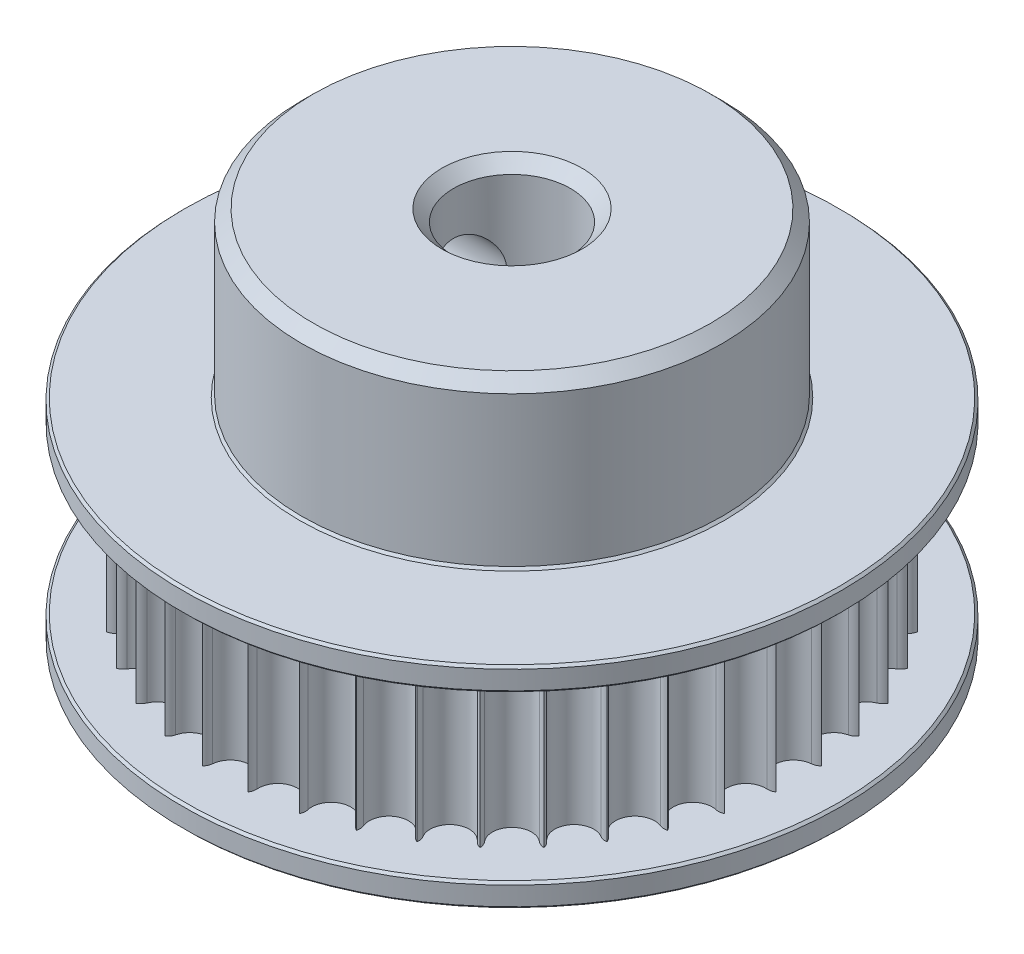
SolidWorks part; units mm, degrees
ref_plane "Front plan" through (0, 0, 0) normal (0, 0, 1) x (1, 0, 0)
ref_plane "Top plan" through (0, 0, 0) normal (0, 1, 0) x (1, 0, 0)
ref_plane "Right plan" through (0, 0, 0) normal (1, 0, 0) x (0, 0, -1)
sketch "Skica2" plane through (0, 0, 0) normal (0, 0, 1) x (1, 0, 0)
  line L0 (9, 8.5) -> (2.5, 8.5)
  line L1 (2.5, 8.5) -> (2.5, -8.5)
  line L2 (2.5, -8.5) -> (6.11, -8.5)
  line L3 (0, -8.5) -> (0, 8.5) construction
  line L4 (0, 8.5) -> (2.5, 8.5)
  line L5 (0, -8.5) -> (2.5, -8.5)
  line L6 (6.11, -8.5) -> (6.11, -7.5)
  line L7 (14.1, 0.5) -> (12.5, 0.5)
  line L8 (12.5, 0.5) -> (12.5, -6.5)
  line L9 (14.1, 0.5) -> (14.1, 1.5)
  line L12 (14.1, -7.5) -> (6.11, -7.5)
  line L13 (14.1, 1.5) -> (9, 1.5)
  line L14 (14.1, -7.5) -> (14.1, -6.5)
  line L15 (12.5, -6.5) -> (14.1, -6.5)
  line L16 (9, 1.5) -> (9, 8.5)
  point P6 (10.105, -7.5)
  point P7 (0, 0)
  dimension "D2" = 1
  dimension "D6" = 28.2
  dimension "D3" = 25
  dimension "D1" = 5
  dimension "D8" = 17
  dimension "D4" = 1
  dimension "D7" = 18
  dimension "D9" = 7
revolve "Revolute" add sketch "Skica2" angle 360 about L3 region at (6.9899, -0.569, 0)
sketch "Sketch2" plane through (0, 0.5, 0) normal (0, -1, 0) x (1, 0, 0)
  line L0 (0, 0) -> (0, 12.0464) construction
  line L1 (0, 0) -> (4.215, 11.7679) construction
  line L3 (0, 0) -> (-2.1557, 12.3127) construction
  circle A1 centre (0, 0) radius 11.2105 construction
  circle A2 centre (0, 0) radius 12 construction
  arc A3 (-0.8326, 11.9711) -> (0.8326, 11.9711) centre (0, 12.0464) ccw
  arc A7 (-1.386, 12.4229) -> (-2.1557, 12.3127) centre (0, 0) ccw
  arc A8 (0, 13.9436) -> (2.1557, 12.3127) centre (0.592, 12.486) cw
  circle A9 centre (0, 0) radius 12.5 construction
  arc A10 (1.386, 12.4229) -> (2.1557, 12.3127) centre (0, 0) cw
  arc A11 (1.386, 12.4229) -> (0.8326, 11.9711) centre (1.3305, 11.926) ccw
  arc A12 (0, 13.9436) -> (-2.1557, 12.3127) centre (-0.592, 12.486) ccw
  arc A13 (-1.386, 12.4229) -> (-0.8326, 11.9711) centre (-1.3305, 11.926) cw
  point P0 (0.8326, 11.926)
  dimension "D2" = 1
  dimension "D4" = 0.836
  dimension "D6" = 25
  dimension "D3" = 1.5733
extrude "Cut-Extrude3" cut sketch "Sketch2" along normal up to surface (7 mm away) up to face at (14.1, -6.5, 0)
pattern_circular "CirPattern1" count 40 over 360 about axis through (0, -8.5, 0) along (0, -1, 0) of "Cut-Extrude3"
sketch "Sketch3" plane through (0, 0, 0) normal (1, 0, 0) x (0, 0, -1)
  line L0 (0, 8.5) -> (0, 0.5) construction
  line L1 (2.5, 8.5) -> (-2.5, 8.5) construction
  circle A0 centre (0, 4.5) radius 1.65
  dimension "D1" = 3.3
extrude "Cut-Extrude2" cut sketch "Sketch3" against normal up to next
chamfer "Chamfer1" distance 1 angle 45 1 edges at (6.11, -7.5, 0)
chamfer "Chamfer2" distance 0.5 angle 45 2 edges at (9, 8.5, 0) (2.5, 8.5, 0)
chamfer "Chamfer3" distance 0.1 angle 45 5 edges at (14.1, -7.5, 0) (14.1, -6.5, 0) (14.1, 0.5, 0) (14.1, 1.5, 0) (9, 1.5, 0)
equation "\"`\"=2"
equation "\"D6@Sketch2\"= \"D3@Skica2\""
